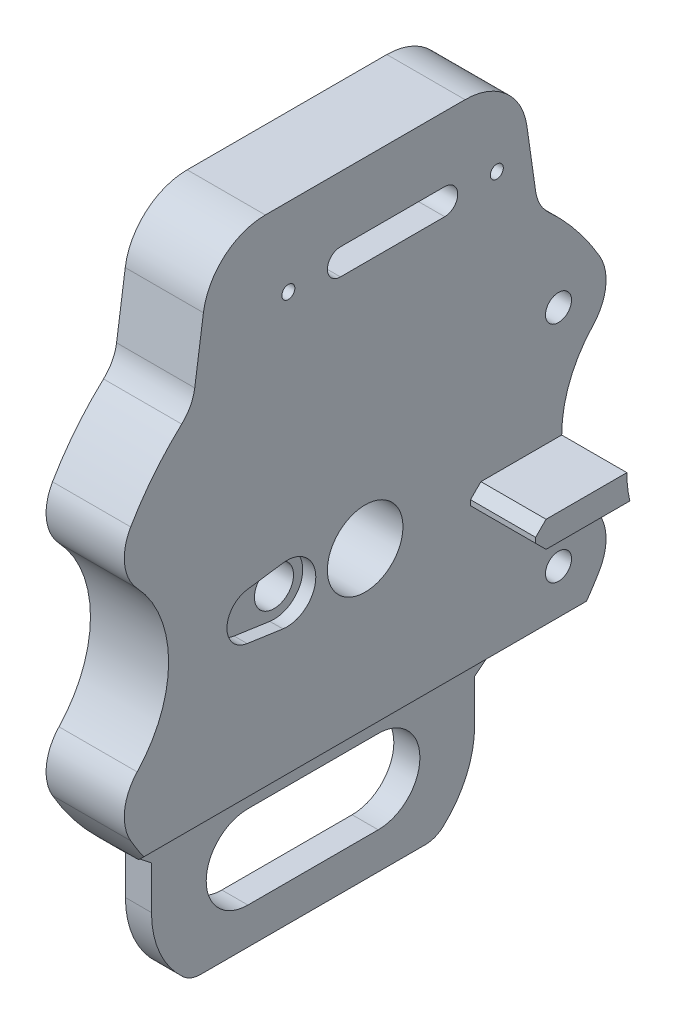
SolidWorks part; units mm, degrees
ref_plane "Płaszczyzna przednia" through (0, 0, 0) normal (0, 0, 1) x (1, 0, 0)
ref_plane "Płaszczyzna górna" through (0, 0, 0) normal (0, 1, 0) x (1, 0, 0)
ref_plane "Płaszczyzna prawa" through (0, 0, 0) normal (1, 0, 0) x (0, 0, -1)
sketch "Szkic1" plane through (0, 0, 0) normal (1, 0, 0) x (0, 0, -1)
  line L0 (-25, -100) -> (25, -100) construction
  line L1 (-25, -84) -> (25, -84)
  line L2 (-25, -116) -> (25, -116)
  line L3 (0, 0) -> (0, -130.3815) construction
  line L4 (0, 0) -> (-120, 0) construction
  line L5 (0, 0) -> (0, 195.8303) construction
  line L6 (0, 0) -> (20.5826, 195.8303) construction
  line L7 (-9.4896, 100) -> (30.5104, 100) construction
  line L8 (-9.4896, 105) -> (30.5104, 105) construction
  line L9 (-9.4896, 95) -> (30.5104, 95) construction
  line L19 (62.0766, 109.386) -> (65.4007, 86.06)
  line L20 (38.3166, 130) -> (-38.3166, 130)
  line L21 (-62.0766, 109.386) -> (-65.4007, 86.06)
  line L28 (-25, -130) -> (25, -130)
  line L33 (-25, -70) -> (25, -70) construction
  line L35 (-25, -130) -> (-43.1384, -130)
  line L36 (62, -100) -> (62, -83.4985)
  line L38 (-62, -100) -> (-62, -83.4985)
  line L39 (25, -130) -> (43.1384, -130)
  line L40 (-62, -82.8995) -> (-69.9497, -74.9497) construction
  line L41 (69.9497, -74.9497) -> (62, -82.8995) construction
  line L42 (-25, -137) -> (25, -137) construction
  line L43 (65, -70) -> (55, -80) construction
  line L44 (55, -100) -> (55, -80) construction
  line L45 (-55, -80) -> (-65, -70) construction
  line L46 (-55, -100) -> (-55, -80) construction
  line L47 (-62, -100) -> (-62, -82.8995) construction
  line L48 (62, -100) -> (62, -82.8995) construction
  circle A0 centre (0, 0) radius 14.5
  arc A1 (-25, -84) -> (-25, -116) centre (-25, -100) ccw
  arc A2 (25, -116) -> (25, -84) centre (25, -100) ccw
  circle A3 centre (0, 0) radius 85.75 construction
  arc A4 (-9.4896, 105) -> (-9.4896, 95) centre (-9.4896, 100) ccw construction
  arc A5 (30.5104, 95) -> (30.5104, 105) centre (30.5104, 100) ccw construction
  arc A26 (-89.9789, -52.1516) -> (-62, -83.4985) centre (0, 0) ccw
  arc A32 (87.4958, -30.51) -> (89.9789, -52.1516) centre (74.1894, -43) cw
  arc A33 (87.4958, -30.51) -> (87.4958, 30.51) centre (120, 0) cw
  arc A34 (89.9789, 52.1516) -> (87.4958, 30.51) centre (74.1894, 43) cw
  arc A35 (70.4086, 76.5417) -> (89.9789, 52.1516) centre (0, 0) cw
  arc A36 (65.4007, 86.06) -> (70.4086, 76.5417) centre (81.2407, 88.3174) ccw
  arc A37 (38.3166, 130) -> (62.0766, 109.386) centre (38.3166, 106) cw
  arc A38 (-38.3166, 130) -> (-62.0766, 109.386) centre (-38.3166, 106) ccw
  arc A39 (-65.4007, 86.06) -> (-70.4086, 76.5417) centre (-81.2407, 88.3174) cw
  arc A40 (-70.4086, 76.5417) -> (-89.9789, 52.1516) centre (0, 0) ccw
  arc A41 (-89.9789, 52.1516) -> (-87.4958, 30.51) centre (-74.1894, 43) ccw
  arc A42 (-87.4958, -30.51) -> (-87.4958, 30.51) centre (-120, 0) ccw
  arc A43 (-87.4958, -30.51) -> (-89.9789, -52.1516) centre (-74.1894, -43) ccw
  arc A54 (89.9789, -52.1516) -> (62, -83.4985) centre (0, 0) cw
  arc A55 (49.8563, -127.4074) -> (62, -100) centre (25, -100) ccw
  arc A56 (-25, -70) -> (-25, -130) centre (-25, -100) ccw construction
  arc A57 (25, -130) -> (25, -70) centre (25, -100) ccw construction
  arc A58 (-62, -100) -> (-49.8563, -127.4074) centre (-25, -100) ccw
  arc A59 (49.8563, -127.4074) -> (43.1384, -130) centre (43.1384, -120) cw
  arc A60 (-62, -100) -> (-25, -137) centre (-25, -100) ccw construction
  arc A61 (25, -137) -> (62, -100) centre (25, -100) ccw construction
  arc A62 (25, -130) -> (55, -100) centre (25, -100) ccw construction
  arc A63 (-55, -100) -> (-25, -130) centre (-25, -100) ccw construction
  arc A64 (-43.1384, -130) -> (-49.8563, -127.4074) centre (-43.1384, -120) cw
  circle A65 centre (74.1894, -43) radius 5
  circle A66 centre (74.1894, 43) radius 5
  point P5 (0, -100)
  point P12 (-74.1894, -43)
  point P13 (0, 0)
  point P19 (10.5104, 100)
  point P24 (-25, -70)
  point P25 (25, -70)
  point P30 (25, -100)
  point P33 (-25, -130)
  point P34 (-25, -100)
  point P43 (-25.5104, 81)
  point P52 (46.6564, -130)
  point P57 (-46.6564, -130)
  point P71 (0, 0)
  point P72 (0, 126)
  dimension "D1" = 29
  dimension "D3" = 16
  dimension "D7" = 171.5
  dimension "D9" = 40
  dimension "D10" = 5
  dimension "D18" = 120
  dimension "D13" = 7
  dimension "D14" = 10
  dimension "D2" = 50
  dimension "D4" = 100
  dimension "D8" = 6
  dimension "D11" = 100
  dimension "D12" = 14
extrude "Dodanie-wyciągnięcie1" add sketch "Szkic1" along normal mid plane 30
hole_wizard "M6 Tapped Hole1" positions "Sketch1" profile "Sketch2" tap size "M6" standard "ISO" end condition through all
sketch "Sketch1" plane through (15, 0, 0) normal (1, 0, 0) x (0, 0, -1)
  line L0 (-81.7008, 100) -> (63.4141, 100) construction
  line L2 (0, 0) -> (0, 150.2111) construction
  line L4 (65.4007, 86.06) -> (62.0766, 109.386) construction
  line L5 (38.3166, 130) -> (-38.3166, 130) construction
  line L7 (10.5104, 105) -> (10.5104, 95) construction
  line L10 (10.5104, 100) -> (0, 0) construction
  point P0 (-29.4896, 100)
  point P2 (50.5104, 100)
  point P42 (0, 0)
  point P43 (-10.5104, 100)
  dimension "D1" = 40
  dimension "D2" = 40
  dimension "D3" = 30
  dimension "D4" = 6
  dimension "D5" = 0
sketch "Sketch2" plane through (15, 100, 29.4896) normal (0, 1, 0) x (0, 0, -1)
  line L0 (0, 0) -> (0, 30)
  line L1 (0, 30) -> (2.5, 30)
  line L2 (2.5, 30) -> (2.5, 0)
  line L5 (2.5, 0) -> (0, 0)
  line L11 (0, -6.35) -> (0, 107.95) construction
  dimension "Thru Tap Drill Dia." = 5
  dimension "Thru Tap Drill Depth" = 30
cosmetic thread "Hole Thread1" parameters "D2"=6
cosmetic thread "Hole Thread2" parameters "D2"=6
sketch "Szkic4" plane through (-15, 0, 0) normal (-1, 0, 0) x (0, 0, 1)
  line L0 (9.4896, 105) -> (-30.5104, 105) construction
  line L1 (9.4896, 105) -> (-30.5104, 105)
  line L2 (9.4896, 95) -> (-30.5104, 95) construction
  line L3 (9.4896, 95) -> (-30.5104, 95)
  arc A0 (9.4896, 95) -> (9.4896, 105) centre (9.4896, 100) ccw construction
  arc A1 (9.4896, 95) -> (9.4896, 105) centre (9.4896, 100) ccw
  arc A2 (-30.5104, 105) -> (-30.5104, 95) centre (-30.5104, 100) ccw construction
  arc A3 (-30.5104, 105) -> (-30.5104, 95) centre (-30.5104, 100) ccw
sketch "Szkic5" plane through (15, 0, 0) normal (-1, 0, 0) x (0, 0, 1)
  line L0 (-75.42, 0) -> (75.42, 0) construction
  line L2 (75.42, 0) -> (44.42, 0)
  line L4 (76.556, -10) -> (44.42, -10)
  line L5 (40.42, -4) -> (40.42, -6)
  line L6 (44.42, 0) -> (40.42, -4)
  line L7 (40.42, -6) -> (44.42, -10)
  line L8 (0, 0) -> (0, -31.7815) construction
  line L9 (-40.42, -6) -> (-44.42, -10)
  line L10 (-44.42, 0) -> (-40.42, -4)
  line L11 (-40.42, -4) -> (-40.42, -6)
  line L12 (-76.556, -10) -> (-44.42, -10)
  line L13 (-75.42, 0) -> (-44.42, 0)
  arc A0 (87.4958, 30.51) -> (87.4958, -30.51) centre (120, 0) ccw construction
  arc A1 (75.42, 0) -> (76.556, -10) centre (120, 0) ccw
  arc A2 (-75.42, 0) -> (-76.556, -10) centre (-120, 0) cw
  point P3 (40.42, -10)
  point P5 (40.42, 0)
  point P21 (-40.42, 0)
  point P22 (-40.42, -10)
  dimension "D1" = 10
  dimension "D2" = 35
extrude "Dodanie-wyciągnięcie3" add sketch "Szkic5" against normal blind 25 contours A2 L12 L9 L11 L10 L13
sketch "Szkic12" plane through (15, 0, 0) normal (1, 0, 0) x (0, 0, -1)
  line L2 (30.5104, 105) -> (-9.4896, 105)
  line L3 (-9.4896, 95) -> (30.5104, 95)
  line L4 (30.5104, 105) -> (-9.4896, 105)
  line L5 (-9.4896, 95) -> (30.5104, 95)
  arc A2 (30.5104, 95) -> (30.5104, 105) centre (30.5104, 100) ccw
  arc A3 (-9.4896, 105) -> (-9.4896, 95) centre (-9.4896, 100) ccw
  arc A4 (30.5104, 95) -> (30.5104, 105) centre (30.5104, 100) ccw
  arc A5 (-9.4896, 105) -> (-9.4896, 95) centre (-9.4896, 100) ccw
  dimension "D1" = 0
extrude "Wytnij-wyciągnięcie2" cut sketch "Szkic12" against normal blind 10 contours A5 L5 A4 L4
sketch "Szkic16" plane through (15, 0, 0) normal (1, 0, 0) x (0, 0, -1)
  line L0 (-25, -116) -> (25, -116) construction
  line L1 (25, -84) -> (-25, -84) construction
  line L3 (-43.1384, -130) -> (43.1384, -130) construction
  line L5 (-25, -116) -> (25, -116)
  line L6 (25, -84) -> (-25, -84)
  line L7 (62, -100) -> (62, -83.4985) construction
  line L8 (-43.1384, -130) -> (43.1384, -130)
  line L9 (-62, -83.4985) -> (-62, -100) construction
  line L10 (-62, -100) -> (62, -100) construction
  line L11 (-76.9155, -70) -> (76.9155, -70)
  line L12 (62, -100) -> (62, -83.4985)
  line L13 (-62, -83.4985) -> (-62, -100)
  arc A0 (-25, -84) -> (-25, -116) centre (-25, -100) ccw construction
  arc A1 (25, -116) -> (25, -84) centre (25, -100) ccw construction
  arc A3 (43.1384, -130) -> (49.8563, -127.4074) centre (43.1384, -120) ccw construction
  arc A4 (-49.8563, -127.4074) -> (-43.1384, -130) centre (-43.1384, -120) ccw construction
  arc A6 (-25, -84) -> (-25, -116) centre (-25, -100) ccw
  arc A7 (25, -116) -> (25, -84) centre (25, -100) ccw
  arc A9 (43.1384, -130) -> (49.8563, -127.4074) centre (43.1384, -120) ccw
  arc A10 (-49.8563, -127.4074) -> (-43.1384, -130) centre (-43.1384, -120) ccw
  arc A14 (-89.9789, -52.1516) -> (-62, -83.4985) centre (0, 0) ccw construction
  arc A15 (-76.9155, -70) -> (-62, -83.4985) centre (0, 0) ccw
  arc A16 (62, -83.4985) -> (89.9789, -52.1516) centre (0, 0) ccw construction
  arc A17 (62, -83.4985) -> (76.9155, -70) centre (0, 0) ccw
  arc A18 (49.8563, -127.4074) -> (62, -100) centre (25, -100) ccw construction
  arc A19 (-62, -100) -> (-49.8563, -127.4074) centre (-25, -100) ccw construction
  arc A20 (49.8563, -127.4074) -> (62, -100) centre (25, -100) ccw
  arc A21 (-62, -100) -> (-49.8563, -127.4074) centre (-25, -100) ccw
extrude "Wytnij-wyciągnięcie4" cut sketch "Szkic16" against normal blind 20
chamfer "Sfazowanie4" distance 10 angle 45 1 edges at (15, -70, 0)
sketch "Szkic17" plane through (15, 0, 0) normal (1, 0, 0) x (0, 0, -1)
  line L2 (0, 0) -> (0, -27.2648) construction
  line L3 (-31.5786, -10.9367) -> (-45.2929, -8.9572)
  line L4 (31.5786, -10.9367) -> (45.2929, -8.9572)
  line L5 (45.2929, 8.9572) -> (31.5786, 10.9367)
  line L6 (-45.2929, 8.9572) -> (-31.5786, 10.9367)
  arc A4 (31.5786, 10.9367) -> (18.9801, -0.8154) centre (30, 0) ccw
  arc A5 (18.9801, -0.8154) -> (31.5786, -10.9367) centre (30, 0) ccw
  circle A6 centre (30, 0) radius 7.5
  circle A7 centre (-30, 0) radius 7.5
  arc A8 (-18.9801, -0.8154) -> (-31.5786, -10.9367) centre (-30, 0) cw
  arc A10 (-31.5786, 10.9367) -> (-18.9801, -0.8154) centre (-30, 0) cw
  arc A11 (45.2929, -8.9572) -> (45.2929, 8.9572) centre (44, 0) ccw
  arc A12 (-45.2929, -8.9572) -> (-45.2929, 8.9572) centre (-44, 0) cw
  point P0 (8.9572, 38.7071)
  point P1 (-0.6678, 49.0253)
  point P3 (-8.9572, 38.7071)
  point P5 (-6.9777, 24.9929)
  point P6 (0, 26)
  point P7 (4.5988, 31.3435)
  point P8 (0, 26)
  point P9 (6.9777, 24.9929)
  point P21 (0, 26)
  point P22 (5.9035, 32.8594)
  dimension "D1" = 14
  dimension "D2" = 30
extrude "Wytnij-wyciągnięcie5" cut sketch "Szkic17" against normal blind 5 contours L3 A12 L6 A10 A8
extrude "Wytnij-wyciągnięcie6" cut sketch "Szkic17<5>" against normal through all contours A7
sketch "Szkic17<5>" plane through (15, 0, 0) normal (1, 0, 0) x (0, 0, -1) same geometry as "Szkic17"
